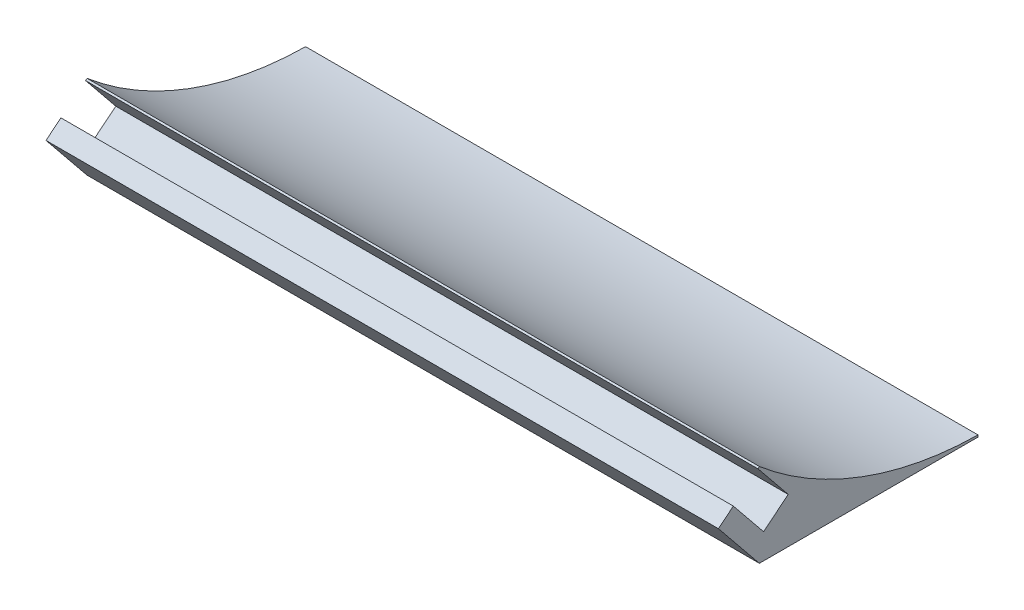
SolidWorks part; units mm, degrees
ref_plane "Front Plane" through (0, 0, 0) normal (0, 0, 1) x (1, 0, 0)
ref_plane "Top Plane" through (0, 0, 0) normal (0, 1, 0) x (1, 0, 0)
ref_plane "Right Plane" through (0, 0, 0) normal (1, 0, 0) x (0, 0, -1)
sketch "Sketch2" plane through (93.0034, 0, 0) normal (-1, 0, 0) x (0, 0, 1)
  line L0 (0, 0) -> (206.9217, 0) construction
  line L1 (207.7413, 5.7736) -> (227.2671, 29.8515) construction
  line L2 (210.0714, 3.884) -> (229.5972, 27.9619) construction
  line L3 (203.0593, 0) -> (227.2671, 29.8515) construction
  line L4 (206.9217, 0) -> (229.5972, 27.9619) construction
  line L5 (207.4988, 5.7128) -> (210.062, 3.6342)
  line L6 (210.0714, 3.884) -> (207.7413, 5.7736) construction
  line L7 (210.0714, 3.884) -> (207.7413, 5.7736) construction
  line L8 (208.9064, 4.8288) -> (208.7804, 4.6735) construction
  line L9 (210.062, 3.6342) -> (213.2113, 7.5177)
  line L10 (207.4988, 5.7128) -> (210.6482, 9.5963)
  line L11 (213.2113, 7.5177) -> (214.7647, 6.258)
  line L12 (214.7647, 6.258) -> (210.5008, 1)
  line L13 (210.5008, 1) -> (187.7413, 1)
  line L14 (210.6482, 9.5963) -> (209.0947, 10.856)
  line L18 (187.7413, 1) -> (187.7413, 1.2)
  arc A0 (210.4928, 9.7223) -> (187.7413, 1.2) centre (187.2699, 37.089) cw
  point P11 (208.7804, 4.6735)
  point P22 (210.2439, 9.9241)
  point P23 (0, 0)
  dimension "D6" = 0.2
  dimension "D9" = 35.8921
  dimension "D1" = 0.2
  dimension "D2" = 0.15
  dimension "D3" = 2
  dimension "D4" = 1
  dimension "D5" = 0.2
  dimension "D7" = 5
  dimension "D8" = 20
extrude "Boss-Extrude1" add sketch "Sketch2" against normal up to surface (70 mm away) contours L14 A0 L18 L13 L12 L11 L9 L5 L10 region at (93.0034, 3.3567, 205.0568)
